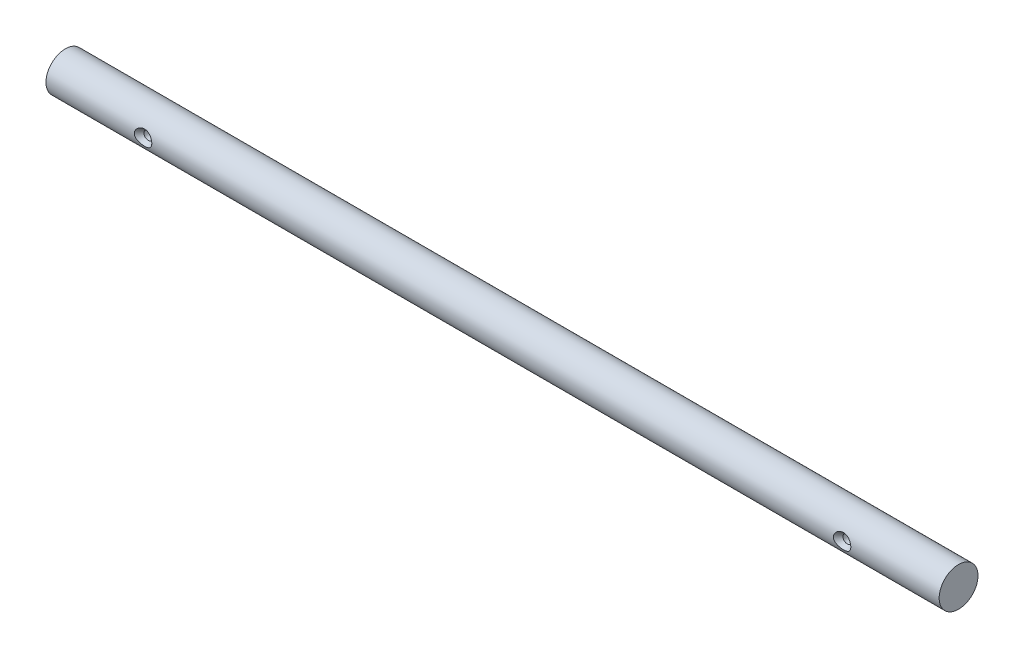
SolidWorks part; units mm, degrees
ref_plane "Front Plane" through (0, 0, 0) normal (0, 0, 1) x (1, 0, 0)
ref_plane "Top Plane" through (0, 0, 0) normal (0, 1, 0) x (1, 0, 0)
ref_plane "Right Plane" through (0, 0, 0) normal (1, 0, 0) x (0, 0, -1)
ref_axis "Axis1" through (88.99, 0, 0) along (-1, 0, 0)
sketch "Sketch1" plane through (0, 0, 0) normal (0, 0, 1) x (1, 0, 0)
  line L0 (0, 0) -> (0, 6.35)
  line L1 (0, -55) -> (0, 55) construction
  line L2 (0, 6.35) -> (292.1, 6.35)
  line L3 (292.1, 6.35) -> (292.1, 0)
  line L4 (55, 0) -> (-55, 0) construction
  line L5 (292.1, 0) -> (0, 0)
  dimension "D1" = 6.35
  dimension "D2" = 292.1
revolve "Revolve1" add sketch "Sketch1" angle 360 about L5
ref_plane "Plane1" through (31.75, 0, 0) normal (1, 0, 0) x (0, 0, -1)
ref_plane "Plane2" through (260.35, 0, 0) normal (1, 0, 0) x (0, 0, -1)
ref_axis "Axis2" through (31.75, 0, 33.081) along (0, 0, -1)
ref_axis "Axis3" through (260.35, 0, 33.081) along (0, 0, -1)
ref_plane "Plane3" through (0, 0, 6.35) normal (0, 0, 1) x (1, 0, 0)
hole_wizard "CSK for #4 Flat Head Machine Screw (100)1" positions "Sketch2" profile "Sketch3" countersink size "#4" standard "ANSI Inch" end condition through all
sketch "Sketch2" plane through (0, 0, 6.35) normal (0, 0, 1) x (1, 0, 0)
  point P0 (31.75, 0)
  point P2 (260.35, 0)
sketch "Sketch3" plane through (31.75, 0, 6.35) normal (1, 0, 0) x (0, -1, 0)
  line L0 (0, 0) -> (0, 12.7)
  line L1 (0, 12.7) -> (1.3894, 12.7)
  line L2 (1.3894, 12.7) -> (1.3894, 1.6889)
  line L3 (1.3894, 1.6889) -> (2.8575, 0)
  line L5 (2.8575, 0) -> (0, 0)
  line L6 (-1.3894, 1.6889) -> (-2.8575, 0) construction
  line L11 (0, -6.35) -> (0, 107.95) construction
  dimension "Thru Hole Dia." = 2.7788
  dimension "Thru Hole Depth" = 12.7
  dimension "Near C'Sink Dia." = 5.715
  dimension "Near C'Sink Angle" = 82
ref_plane "Plane4" through (0, 0, -6.35) normal (0, 0, -1) x (-1, 0, 0)
